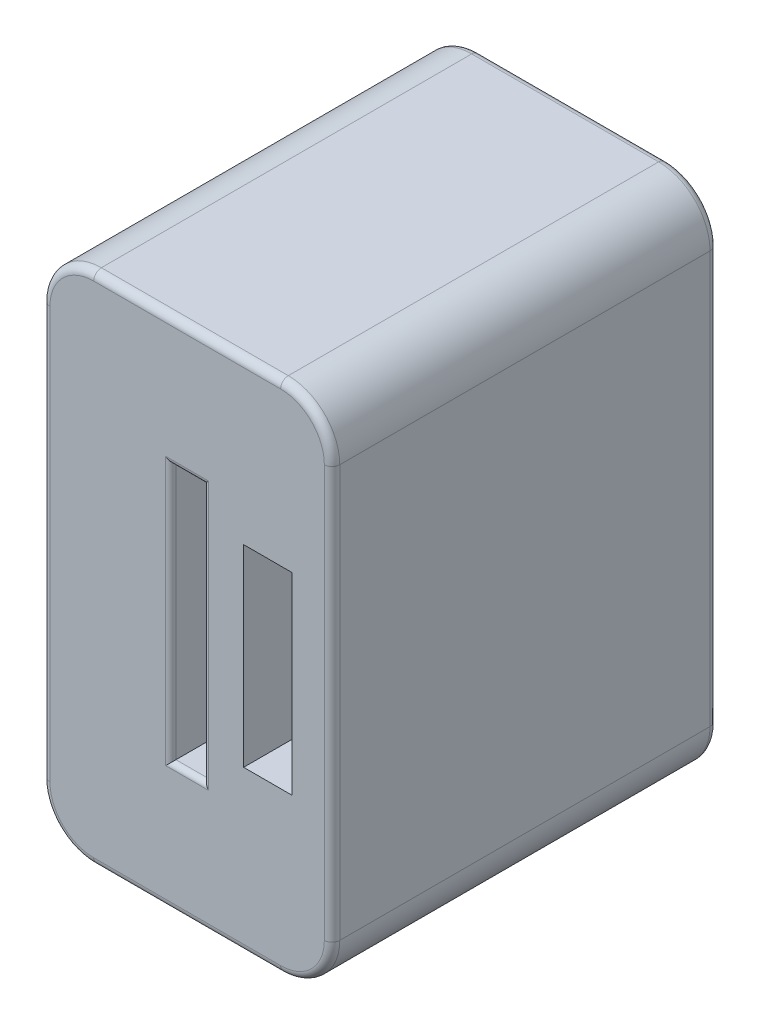
SolidWorks part; units mm, degrees
ref_plane "Front Plane" through (0, 0, 0) normal (0, 0, 1) x (1, 0, 0)
ref_plane "Top Plane" through (0, 0, 0) normal (0, 1, 0) x (1, 0, 0)
ref_plane "Right Plane" through (0, 0, 0) normal (1, 0, 0) x (0, 0, -1)
sketch "Sketch1" plane through (0, 0, 0) normal (0, 0, 1) x (1, 0, 0)
  line L0 (-14.3129, -25.4254) -> (-14.3129, 25.4254)
  line L1 (-1.6129, -12.7254) -> (1.6129, -12.7254)
  line L2 (-1.6129, -12.7254) -> (-1.6129, 12.7254)
  line L3 (-1.6129, 12.7254) -> (1.6129, 12.7254)
  line L4 (1.6129, -12.7254) -> (1.6129, 12.7254)
  line L5 (-1.6129, -12.7254) -> (1.6129, 12.7254) construction
  line L6 (-1.6129, 12.7254) -> (1.6129, -12.7254) construction
  line L7 (-14.3129, 25.4254) -> (14.3129, 25.4254)
  line L8 (14.3129, -25.4254) -> (14.3129, 25.4254)
  line L9 (-14.3129, -25.4254) -> (14.3129, -25.4254)
  point P0 (0, 0)
  dimension "D1" = 3.2258
  dimension "D2" = 25.4508
  dimension "D3" = 12.7
extrude "Boss-Extrude1" add sketch "Sketch1" along normal mid plane 38.1
fillet "Fillet1" radius 5.08 4 edges at (-14.3129, -25.4254, 0) (14.3129, -25.4254, 0) (-14.3129, 25.4254, 0) (14.3129, 25.4254, 0)
fillet "Fillet3" radius 0.762 16 edges at (12.825, -23.9375, 19.05) (0, -25.4254, 19.05) (-12.825, -23.9375, 19.05) (-14.3129, 0, 19.05) (-12.825, 23.9375, 19.05) (0, 25.4254, 19.05) (12.825, 23.9375, 19.05) (12.825, -23.9375, -19.05) (0, -25.4254, -19.05) (-12.825, -23.9375, -19.05) (-14.3129, 0, -19.05) (-12.825, 23.9375, -19.05) (0, 25.4254, -19.05) (12.825, 23.9375, -19.05) (14.3129, 0, 19.05) (14.3129, 0, -19.05)
fillet "Fillet4" radius 0.508 8 edges at (0, 12.7254, 19.05) (-1.6129, 0, 19.05) (0, -12.7254, 19.05) (1.6129, 0, 19.05) (0, -12.7254, -19.05) (1.6129, 0, -19.05) (0, 12.7254, -19.05) (-1.6129, 0, -19.05)
ref_plane "Plane1" through (7.9629, 0, 0) normal (1, 0, 0) x (0, 0, -1)
sketch "Sketch2" plane through (7.9629, 0, 0) normal (1, 0, 0) x (0, 0, -1)
  line L0 (0, 9.525) -> (-19.05, 9.525)
  line L1 (-19.05, -20.3454) -> (-19.05, 20.3454) construction
  line L2 (0, -9.525) -> (-19.05, -9.525)
  line L3 (-19.05, -9.525) -> (-19.05, 9.525)
  circle A0 centre (0, 0) radius 9.525
  point P9 (0, 0)
  point P10 (-19.05, 13.2724)
  dimension "D1" = 19.05
extrude "Cut-Extrude1" cut sketch "Sketch2" against normal mid plane 6.35 contours A0 region at (7.9629, 0, 0)
extrude "Cut-Extrude2" cut sketch "Sketch2<3>" against normal mid plane 4.7625 contours A0 L0 L3 L2 region at (7.9629, 0, 13.0701)
sketch "Sketch2<3>" plane through (7.9629, 0, 0) normal (1, 0, 0) x (0, 0, -1) same geometry as "Sketch2"
